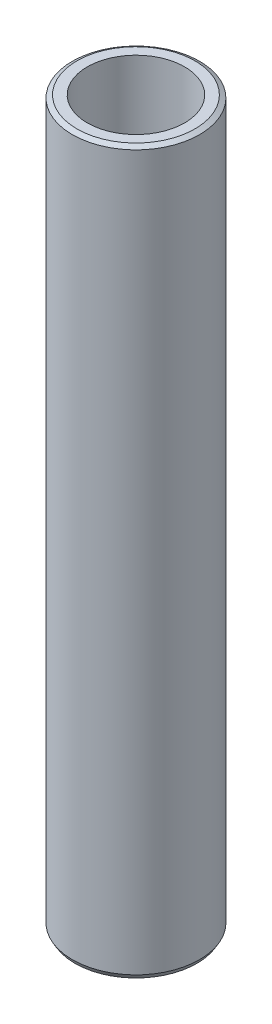
SolidWorks part; units mm, degrees
ref_plane "Front Plane" through (0, 0, 0) normal (0, 0, 1) x (1, 0, 0)
ref_plane "Top Plane" through (0, 0, 0) normal (0, 1, 0) x (1, 0, 0)
ref_plane "Right Plane" through (0, 0, 0) normal (1, 0, 0) x (0, 0, -1)
sketch "Sketch1" plane through (0, 0, 0) normal (0, 1, 0) x (1, 0, 0)
  circle A0 centre (0, 0) radius 35
  dimension "SHAFT_OD" = 70
extrude "Boss-Extrude1" add sketch "Sketch1" along normal blind 397.0389
sketch "Sketch2" plane through (0, 0, 0) normal (0, 1, 0) x (1, 0, 0)
  circle A0 centre (0, 0) radius 26.7614
  dimension "BORE_D" = 53.5228
extrude "Cut-Extrude1" cut sketch "Sketch2" along normal through all
chamfer "Chamfer1" distance 1.4656 angle 60 2 edges at (0, 397.0389, 35) (0, 0, 35) first distance on face at (0, 397.0389, 35) first distance on face at (0, 0, 26.7614)
